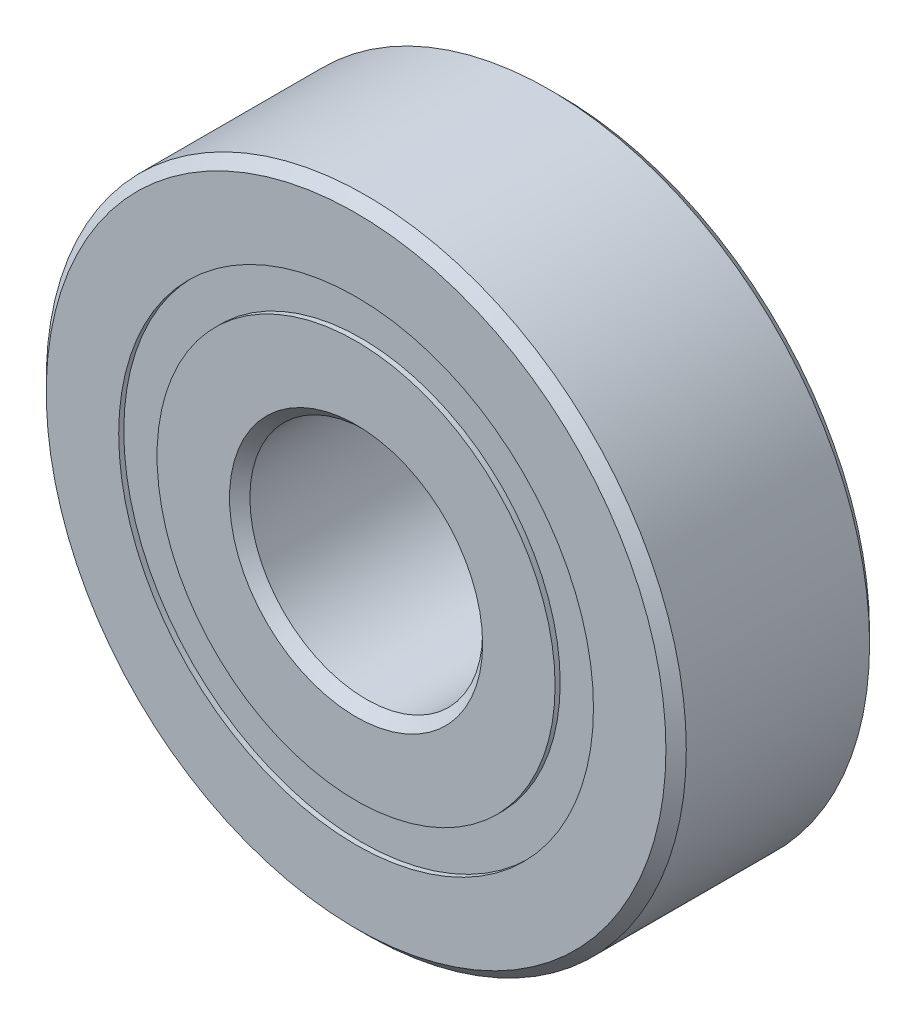
SolidWorks part; units mm, degrees
material "Plain Carbon Steel"
ref_plane "Front Plane" through (0, 0, 0) normal (0, 0, 1) x (1, 0, 0)
ref_plane "Top Plane" through (0, 0, 0) normal (0, 1, 0) x (1, 0, 0)
ref_plane "Right Plane" through (0, 0, 0) normal (1, 0, 0) x (0, 0, -1)
sketch "Sketch1" plane through (0, 0, 0) normal (1, 0, 0) x (0, 0, -1)
  line L0 (-3.5, 0) -> (3.5, 0) construction
  line L1 (0, 11) -> (0, -11) construction
  line L2 (3.15, 11) -> (-3.15, 11)
  line L3 (-3.15, 11) -> (-3.5, 10.65)
  line L4 (-3.5, 10.65) -> (-3.5, 8.1593)
  line L5 (-3.5, 8.1593) -> (-1.5556, 8.1593)
  line L6 (3.5, 8.1593) -> (1.5556, 8.1593)
  line L7 (3.5, 10.65) -> (3.5, 8.1593)
  line L8 (3.15, 11) -> (3.5, 10.65)
  line L9 (0, 11) -> (0, 7.5) construction
  line L10 (0, 7.5) -> (0, 4) construction
  arc A0 (-1.5556, 8.1593) -> (1.5556, 8.1593) centre (0, 7.5) cw
  point P14 (0, 4)
  dimension "Width" = 7
  dimension "OD" = 22
  dimension "D1" = 45
  dimension "D2" = 0.35
  dimension "Shaft Dia" = 8
  dimension "D3" = 3.1111
  dimension "D4" = 0.6593
revolve "Revolve1" add sketch "Sketch1" angle 360 about L0
sketch "Sketch3" plane through (0, 0, 0) normal (1, 0, 0) x (0, 0, -1)
  line L0 (-3.5, 6.8407) -> (-1.5556, 6.8407)
  line L1 (0, 11) -> (0, -11) construction
  line L2 (-3.5, 10.65) -> (-3.5, 8.1593) construction
  line L3 (-3.5, 6.8407) -> (-3.5, 4.35)
  line L4 (-3.15, 11) -> (-3.5, 10.65) construction
  line L5 (-3.5, 4.35) -> (-3.15, 4)
  line L6 (-3.15, 4) -> (3.15, 4)
  line L7 (3.15, 11) -> (3.15, -11) construction
  line L8 (3.15, 4) -> (3.5, 4.35)
  line L9 (3.5, -10.65) -> (3.5, 10.65) construction
  line L10 (3.5, 4.35) -> (3.5, 6.8407)
  line L11 (3.5, 6.8407) -> (1.5556, 6.8407)
  line L13 (3.15, 11) -> (3.5, 10.65) construction
  arc A0 (1.5556, 8.1593) -> (-1.5556, 8.1593) centre (0, 7.5) ccw construction
  arc A1 (1.5556, 6.8407) -> (-1.5556, 6.8407) centre (0, 7.5) cw
revolve "Revolve3" add sketch "Sketch3" angle 360 about L0
sketch "Sketch4" plane through (0, 0, 0) normal (1, 0, 0) x (0, 0, -1)
  line L0 (-1.6895, 7.5) -> (1.6895, 7.5)
  arc A2 (-1.6895, 7.5) -> (1.6895, 7.5) centre (0, 7.5) cw
  arc A3 (1.5556, 8.1593) -> (-1.5556, 8.1593) centre (0, 7.5) ccw construction
revolve "Revolve4" add sketch "Sketch4" angle 360 about L0
ref_axis "Axis1" through (0, 0, -3.5) along (0, 0, 1)
pattern_circular "CirPattern1" count 12 every 30 about axis through (0, 0, -3.5) along (0, 0, 1) of bodies 104
sketch "Sketch5" plane through (0, 0, 0) normal (1, 0, 0) x (0, 0, -1)
  line L0 (-3.5, 8.1593) -> (-1.5556, 8.1593) construction
  line L1 (-3.325, 8.1593) -> (-1.6895, 8.1593)
  line L2 (-3.325, 8.1593) -> (-3.325, 6.8407)
  line L3 (-3.325, 6.8407) -> (-1.6895, 6.8407)
  line L4 (-1.6895, 8.1593) -> (-1.6895, 6.8407)
  line L5 (-3.5, 6.8407) -> (-1.5556, 6.8407) construction
  line L6 (3.5, 8.1593) -> (1.5556, 8.1593) construction
  line L7 (3.325, 8.1593) -> (1.6895, 8.1593)
  line L8 (3.325, 8.1593) -> (3.325, 6.8407)
  line L9 (3.325, 6.8407) -> (1.6895, 6.8407)
  line L10 (1.6895, 8.1593) -> (1.6895, 6.8407)
  line L11 (3.5, 6.8407) -> (1.5556, 6.8407) construction
  line L12 (-3.15, 11) -> (-3.5, 10.65) construction
  point P18 (-3.325, 10.825)
revolve "Revolve5" add sketch "Sketch5" angle 360 about L0
sketch "Sketch6" plane through (0, 0, 0) normal (1, 0, 0) x (0, 0, -1)
  line L0 (3.5, 0) -> (-3.5, 0) construction
  line L1 (3.5, 8.1593) -> (2.4, 8.1593)
  line L2 (3.5, 8.1593) -> (3.5, 9.5)
  line L3 (3.5, 9.5) -> (2.4, 9.5)
  line L4 (2.4, 8.1593) -> (2.4, 9.5)
  dimension "Th" = 1.1
  dimension "Flange OD" = 19
revolve "Revolve6" [suppressed] add sketch "Sketch6" angle 360 about L0
equation "\"D2@Sketch1\" = \"Width@Sketch1\"*.05"
equation "\"D3@Sketch1\" = \"Width@Sketch1\"/2.25"
equation "\"D4@Sketch1\" = (((\"OD@Sketch1\"-\"Width@Sketch1\")/2)/3.25)/3.5"
equation "\"D2@CirPattern1\" = 360/\"Balls@CirPattern1\""
